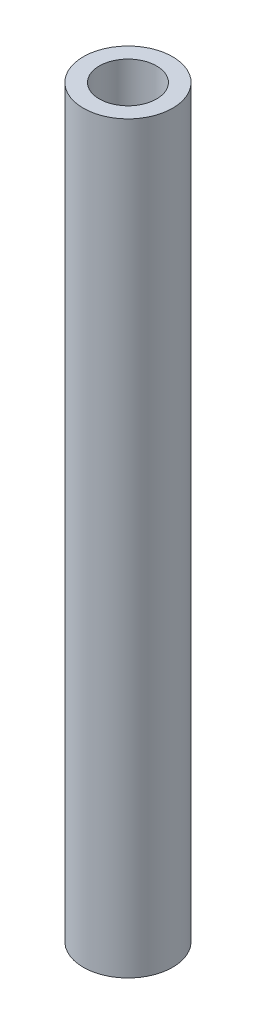
SolidWorks part; units mm, degrees
ref_plane "Plan de face" through (0, 0, 0) normal (0, 0, 1) x (1, 0, 0)
ref_plane "Plan de dessus" through (0, 0, 0) normal (0, 1, 0) x (1, 0, 0)
ref_plane "Plan de droite" through (0, 0, 0) normal (1, 0, 0) x (0, 0, -1)
sketch "Esquisse1" plane through (0, 0, 0) normal (0, 1, 0) x (1, 0, 0)
  circle A0 centre (-34.3904, -12.561) radius 3.85
  circle A1 centre (-34.3904, -12.561) radius 6
  dimension "D1" = 12
  dimension "D2" = 7.7
extrude "Boss.-Extru.1" add sketch "Esquisse1" along normal blind 100 contours A1
extrude "Enlèv. mat.-Extru.1" cut sketch "Esquisse1<3>" along normal blind 100 contours A0
sketch "Esquisse1<3>" plane through (0, 0, 0) normal (0, 1, 0) x (1, 0, 0) same geometry as "Esquisse1"
